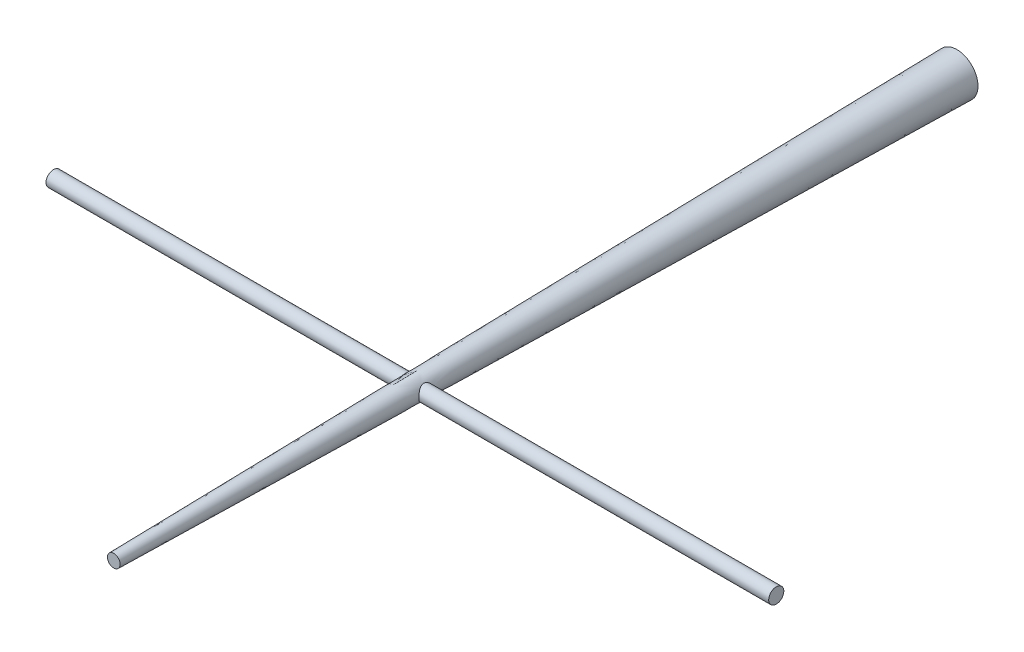
SolidWorks part; units mm, degrees
ref_plane "Front Plane" through (0, 0, 0) normal (0, 0, 1) x (1, 0, 0)
ref_plane "Top Plane" through (0, 0, 0) normal (0, 1, 0) x (1, 0, 0)
ref_plane "Right Plane" through (0, 0, 0) normal (1, 0, 0) x (0, 0, -1)
sketch "Sketch1" plane through (0, 0, 0) normal (0, 0, 1) x (1, 0, 0)
  circle A0 centre (0, 0) radius 175
  dimension "D1" = 350
extrude "Boss-Extrude1" add sketch "Sketch1" along normal blind 7000 draft 1
sketch "Sketch2" plane through (0, 0, 0) normal (1, 0, 0) x (0, 0, -1)
  circle A0 centre (-4500, 0) radius 62.7468
  dimension "D1" = 4500
extrude "Boss-Extrude2" add sketch "Sketch2" along normal blind 3000 and the other way blind 3000
